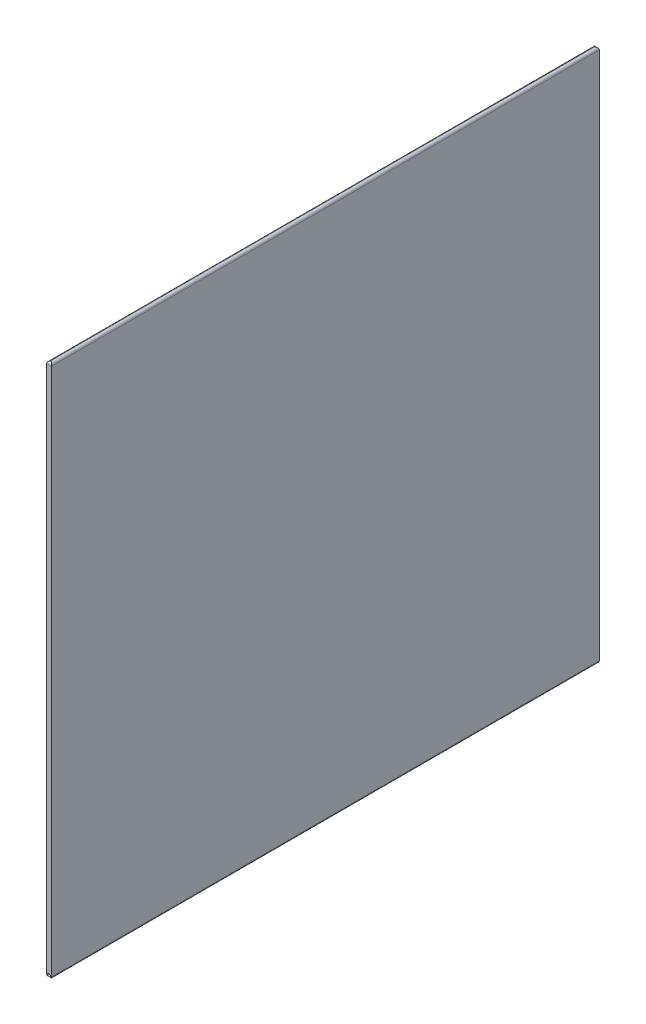
SolidWorks part; units mm, degrees
material "201 退火不锈钢 (SS)"
ref_plane "前视基准面" through (0, 0, 0) normal (0, 0, 1) x (1, 0, 0)
ref_plane "上视基准面" through (0, 0, 0) normal (0, 1, 0) x (1, 0, 0)
ref_plane "右视基准面" through (0, 0, 0) normal (1, 0, 0) x (0, 0, -1)
sketch "草图1" plane through (0, 0, 0) normal (1, 0, 0) x (0, 0, -1)
  line L1 (-171.5, 167) -> (171.5, 167)
  line L2 (-171.5, 167) -> (-171.5, -167)
  line L3 (-171.5, -167) -> (171.5, -167)
  line L4 (171.5, 167) -> (171.5, -167)
  line L5 (-171.5, 167) -> (171.5, -167) construction
  line L6 (-171.5, -167) -> (171.5, 167) construction
  point P0 (0, 0)
  dimension "D1" = 343
  dimension "D2" = 334
extrude "凸台-拉伸1" add sketch "草图1" along normal blind 3
sketch "草图3" plane through (0, 0, 171.5) normal (0, 0, 1) x (1, 0, 0)
  circle A0 centre (1.5, -165.5) radius 1
extrude "切除-拉伸1" cut sketch "草图3" against normal through all
fillet "圆角1" radius 1.5 4 edges at (1.5, -167, 171.5) (3, -167, 0) (1.5, -167, -171.5) (0, -167, 0)
fillet "圆角2" radius 1.5 4 edges at (1.5, 167, -171.5) (3, 167, 0) (1.5, 167, 171.5) (0, 167, 0)
